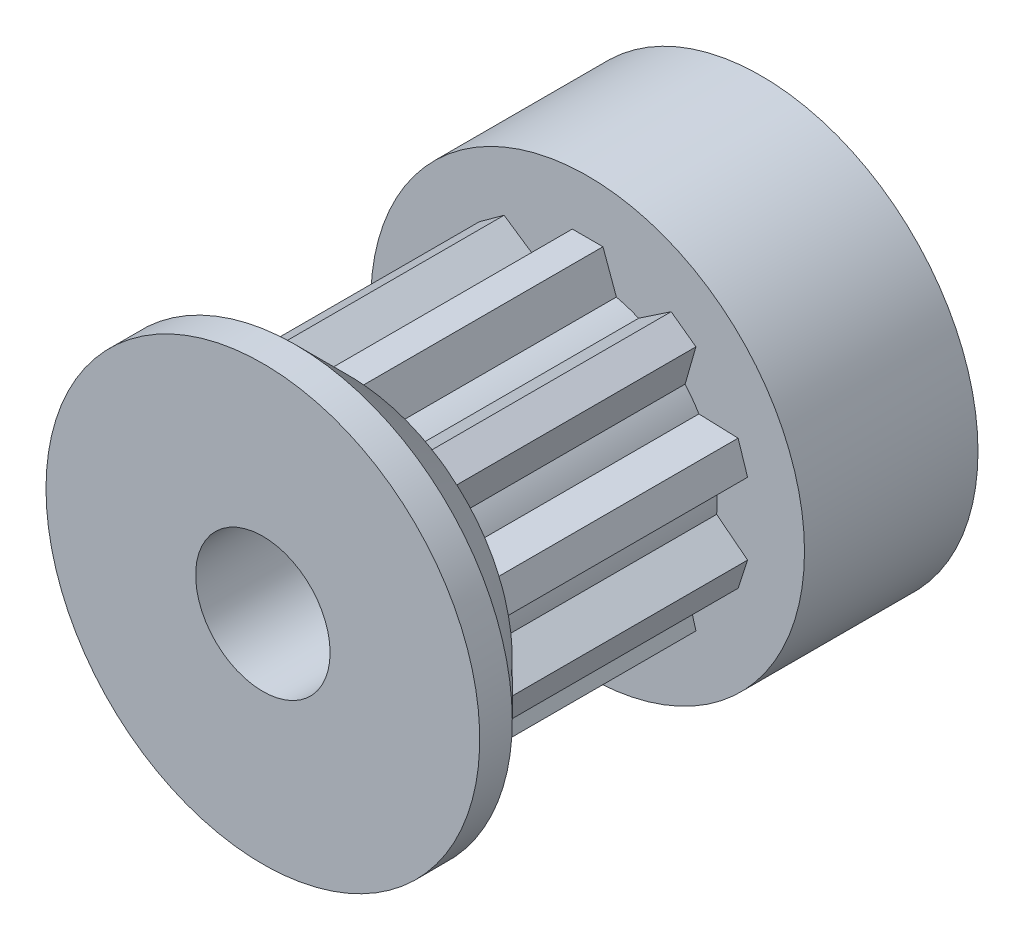
SolidWorks part; units mm, degrees
material "ABS"
ref_plane "Front (1)" through (0, 0, 0) normal (0, 0, 1) x (1, 0, 0)
ref_plane "Top (2)" through (0, 0, 0) normal (0, 1, 0) x (1, 0, 0)
ref_plane "Right (3)" through (0, 0, 0) normal (1, 0, 0) x (0, 0, -1)
ref_axis "X Axis" through (13.5064, 0, 0) along (-1, 0, 0)
ref_axis "Y Axis" through (0, 12.3593, 0) along (0, -1, 0)
ref_axis "Z Axis" through (0, 0, 14.1119) along (0, 0, -1)
imported_body "Imported1" [suppressed]
delete or keep bodies "Body-Delete1" [suppressed] type delete bodies bodies 116
sketch "Sketch1" plane through (0, 0, 0) normal (0, 0, 1) x (1, 0, 0)
  circle A0 centre (0, 0) radius 10
  dimension "D1" = 10
extrude "Base" add sketch "Sketch1" along normal blind 8 separate body
sketch "Sketch3" plane through (0, 0, 0) normal (0, 0, 1) x (1, 0, 0)
  line L0 (-0.7063, 7.525) -> (0.7063, 7.525)
  line L1 (0.7063, 7.525) -> (1.325, 5.825)
  line L2 (1.325, 5.825) -> (-1.325, 5.825)
  line L3 (-1.325, 5.825) -> (-0.7063, 7.525)
  line L4 (0, 7.525) -> (0, 0) construction
  line L5 (0, 0) -> (3.549, 0) construction
  point P11 (0, 5.825)
  dimension "D1" = 1.4125
  dimension "D2" = 1.7
  dimension "D3" = 2.65
  dimension "D4" = 7.525
  dimension "D5" = 40
extrude "Tooth" add sketch "Sketch3" along normal blind 20
sketch "Sketch11" plane through (0, 0, 0) normal (1, 0, 0) x (0, 0, -1)
  line L0 (-20, 5.825) -> (-8, 5.825) construction
  line L1 (-22.975, 10) -> (-21.475, 10)
  line L2 (-22.975, 10) -> (-22.975, 5.825)
  line L3 (-22.975, 5.825) -> (-19, 5.825)
  line L4 (-21.475, 10) -> (-19, 7.525)
  line L6 (0, 10) -> (-8, 10) construction
  line L7 (0, 0) -> (-18.8336, 0) construction
  line L8 (-19, 7.525) -> (-19, 5.825)
  line L9 (-20, 7.525) -> (-8, 7.525) construction
  dimension "D1" = 45
  dimension "D2" = 1.5
  dimension "D3" = 11
revolve "Revolve1" add sketch "Sketch11" angle 360 about L7
sketch "Sketch2" plane through (0, 0, 0) normal (0, 0, 1) x (1, 0, 0)
  circle A0 centre (0, 0) radius 5.9738
  dimension "D1" = 5.9738
extrude "Root" add sketch "Sketch2" along normal up to surface (22.975 mm away) up to face at (-5.825, 0, 22.975)
pattern_circular "Teeth" count 10 over 360 about axis through (0, 0, 14.1119) along (0, 0, -1) of "Tooth"
sketch "Sketch4" plane through (0, 0, 0) normal (0, 0, 1) x (1, 0, 0)
  circle A0 centre (0, 0) radius 3.1
  dimension "D1" = 3.1
extrude "Shaft Hole" cut sketch "Sketch4" along normal through all
hole_wizard "M5 Tapped Hole1" positions "3DSketch1" profile "Sketch5" tap size "M5" standard "ISO" end condition up to next
sketch3d "3DSketch1"
  line L1 (-8.6603, -5, 4) -> (0, 0, 4) construction
  line L3 (0, 0, 14.1119) -> (0, 0, 4.4761) construction
  line L5 (0, 0, 4) -> (0, 11.4342, 4) construction
  point P0 (-8.6603, -5, 4)
  dimension "D1" = 120
  dimension "D2" = 4
sketch "Sketch5" plane through (-8.6603, -5, 4) normal (0, 0, 1) x (0.5, -0.866, 0)
  line L0 (0, 0) -> (0, 6.9)
  line L1 (0, 6.9) -> (2.1, 6.9)
  line L2 (2.1, 6.9) -> (2.1, 0)
  line L5 (2.1, 0) -> (0, 0)
  line L11 (0, -6.35) -> (0, 107.95) construction
  dimension "Thru Tap Drill Dia." = 4.2
  dimension "Thru Tap Drill Depth" = 6.9
cosmetic thread "Hole Thread2" parameters "D2"=5
sketch "Sketch6" plane through (0, 0, 0) normal (0, 0, 1) x (1, 0, 0)
  line L0 (-5.1239, 0.2749) -> (-2.3239, -4.5749)
  line L1 (-5.1239, 0.2749) -> (-7.2024, -0.9251)
  line L2 (-2.3239, -4.5749) -> (-4.4024, -5.7749)
  line L3 (-7.2024, -0.9251) -> (-4.4024, -5.7749)
  line L5 (-8.6603, -5) -> (0, 0) construction
  point P9 (-3.7239, -2.15)
  dimension "D1" = 4.3
  dimension "D2" = 5.6
  dimension "D3" = 2.4
extrude "Slot for nut" cut sketch "Sketch6" along normal blind 6
sketch "Sketch7" plane through (-3.7239, -2.15, 0) normal (-0.866, -0.5, 0) x (0, 0, 1)
  line L1 (2.44, -2.702) -> (5.56, -2.702)
  line L2 (5.56, -2.702) -> (7.12, 0)
  line L3 (7.12, 0) -> (5.56, 2.702)
  line L4 (5.56, 2.702) -> (2.44, 2.702)
  line L5 (2.44, 2.702) -> (0.88, 0)
  line L6 (0.88, 0) -> (2.44, -2.702)
  circle A0 centre (4, 0) radius 3.12 construction
  dimension "D1" = 3.12
extrude "Pocket for nut" cut sketch "Sketch7" against normal blind 0.3 and the other way up to surface (2.4 mm away) other way up to face at (-5.8024, -3.35, 3.3167)
equation "\"D1@Sketch4\" = \"Motor Shaft Radius\"/2+.1"
